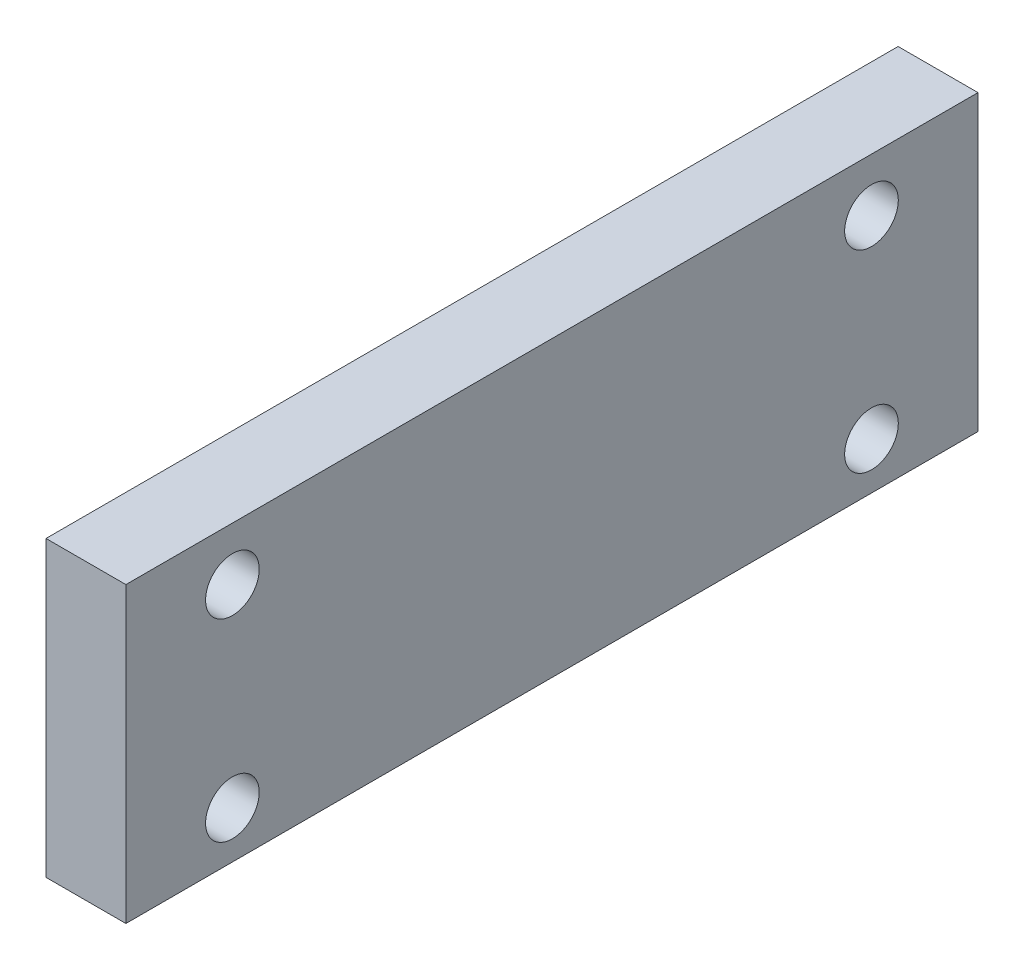
SolidWorks part; units mm, degrees
ref_plane "Front Plane" through (0, 0, 0) normal (0, 0, 1) x (1, 0, 0)
ref_plane "Top Plane" through (0, 0, 0) normal (0, 1, 0) x (1, 0, 0)
ref_plane "Right Plane" through (0, 0, 0) normal (1, 0, 0) x (0, 0, -1)
sketch "Sketch1" plane through (0, 0, 0) normal (1, 0, 0) x (0, 0, -1)
  line L1 (50.8, -17.5) -> (-50.8, -17.5)
  line L2 (50.8, -17.5) -> (50.8, 17.5)
  line L3 (50.8, 17.5) -> (-50.8, 17.5)
  line L4 (-50.8, -17.5) -> (-50.8, 17.5)
  line L5 (50.8, -17.5) -> (-50.8, 17.5) construction
  line L6 (50.8, 17.5) -> (-50.8, -17.5) construction
  point P0 (0, 0)
  dimension "D1" = 101.6
  dimension "D2" = 35
extrude "Boss-Extrude1" add sketch "Sketch1" along normal mid plane 9.525
sketch "Sketch2" plane through (4.7625, 0, 0) normal (1, 0, 0) x (0, 0, -1)
  line L0 (50.8, 17.5) -> (-50.8, 17.5) construction
  line L1 (-50.8, 17.5) -> (-50.8, -17.5) construction
  line L2 (50.8, -17.5) -> (50.8, 17.5) construction
  circle A0 centre (-38.1, 11.15) radius 3.2
  circle A1 centre (38.1, 11.15) radius 3.2
  circle A2 centre (-38.1, -11.9) radius 3.2
  circle A3 centre (38.1, -11.9) radius 3.2
  dimension "D1" = 6.4
  dimension "D2" = 6.35
  dimension "D3" = 12.7
  dimension "D4" = 6.4
  dimension "D5" = 12.7
  dimension "D6" = 6.4
  dimension "D7" = 6.4
  dimension "D10" = 6.35
  dimension "D8" = 23.05
  dimension "D9" = 23.05
extrude "Cut-Extrude1" cut sketch "Sketch2" against normal through all
